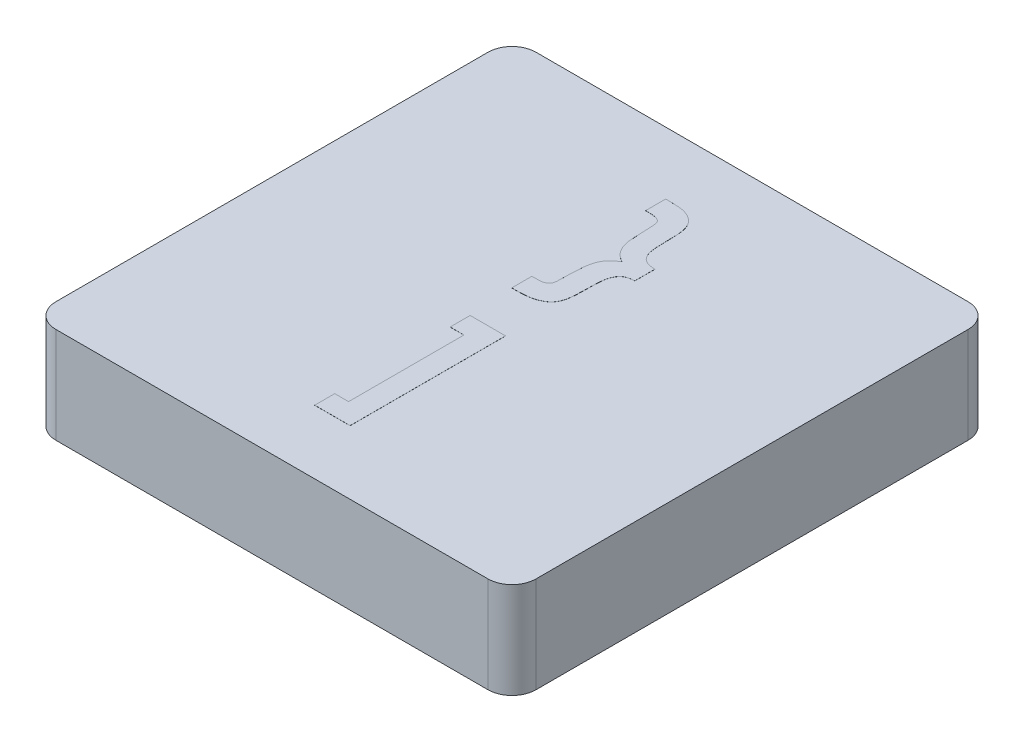
SolidWorks part; units mm, degrees
ref_plane "Front Plane" through (0, 0, 0) normal (0, 0, 1) x (1, 0, 0)
ref_plane "Top Plane" through (0, 0, 0) normal (0, 1, 0) x (1, 0, 0)
ref_plane "Right Plane" through (0, 0, 0) normal (1, 0, 0) x (0, 0, -1)
sketch "Sketch1" plane through (0, 0, 0) normal (0, 1, 0) x (1, 0, 0)
  line L0 (0, 0) -> (12.7, 0)
  line L1 (12.7, 0) -> (12.7, 12.7)
  line L2 (12.7, 12.7) -> (0, 12.7)
  line L3 (0, 12.7) -> (0, 0)
  dimension "D1" = 12.7
  dimension "D2" = 12.7
extrude "Boss-Extrude1" add sketch "Sketch1" along normal blind 2.54
fillet "Fillet1" radius 0.635 4 edges at (0, 1.27, -12.7) (12.7, 1.27, -12.7) (12.7, 1.27, 0) (0, 1.27, 0)
shell "Shell1" thickness 0.635 removed face at (6.35, 0, -6.35)
sketch "Sketch2" plane through (0, 1.905, 0) normal (0, -1, 0) x (-1, 0, 0)
  line L0 (-0.635, 6.35) -> (-12.065, 6.35) construction
  line L1 (-0.635, 12.065) -> (-0.635, 0.635) construction
  line L2 (-12.065, 0.635) -> (-12.065, 12.065) construction
  line L3 (-6.35, 0.635) -> (-6.35, 12.065) construction
  line L4 (-0.635, 0.635) -> (-12.065, 0.635) construction
  line L5 (-12.065, 12.065) -> (-0.635, 12.065) construction
  circle A0 centre (-6.35, 6.35) radius 2.54
  dimension "D1" = 5.08
extrude "Boss-Extrude2" add sketch "Sketch2" along normal up to surface (1.905 mm away) up to face at (6.35, 0, -6.35)
sketch "Sketch4" plane through (0, 2.54, 0) normal (0, 1, 0) x (1, 0, 0)
  line L0 (0, 12.065) -> (0, 0.635) construction
  line L1 (12.065, 12.7) -> (0.635, 12.7) construction
  line L2 (0.635, 0) -> (12.065, 0) construction
  text T0 "<b>]</b>"
  text T1 "<b>}</b>"
  dimension "D1" = 5.715
  dimension "D2" = 5.715
  dimension "D3" = 4.826
  dimension "D4" = 2.54
extrude "Boss-Extrude4" add sketch "Sketch4" along normal blind 0.0025
